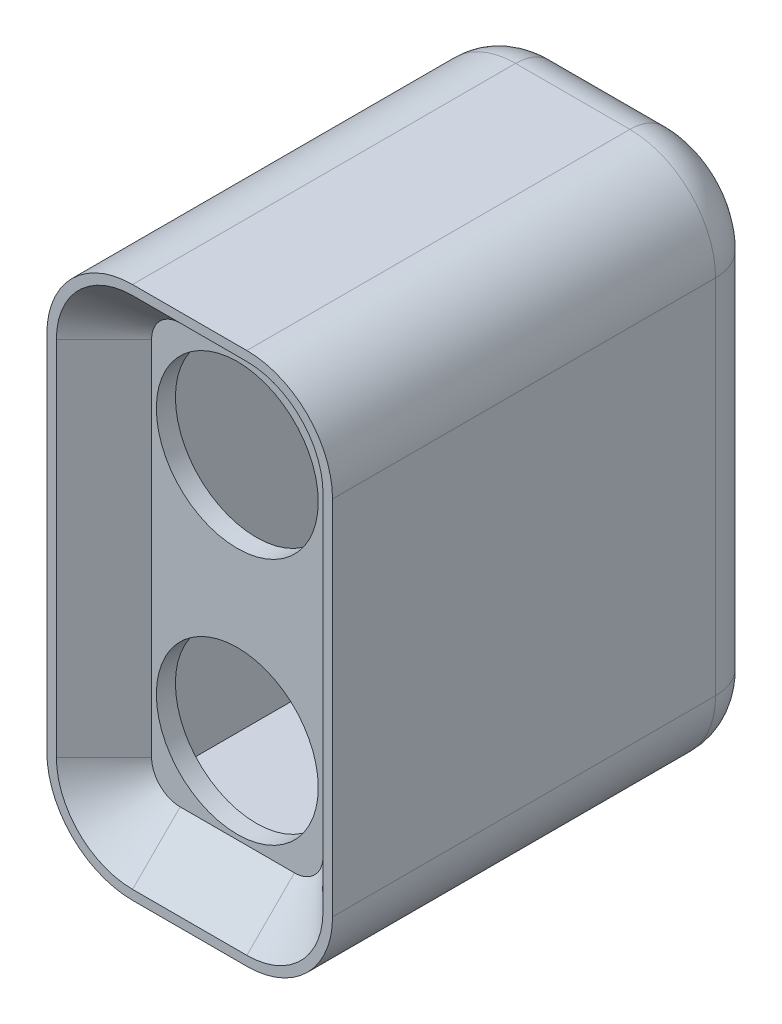
SolidWorks part; units mm, degrees
ref_plane "Front Plane" through (0, 0, 0) normal (0, 0, 1) x (1, 0, 0)
ref_plane "Top Plane" through (0, 0, 0) normal (0, 1, 0) x (1, 0, 0)
ref_plane "Right Plane" through (0, 0, 0) normal (1, 0, 0) x (0, 0, -1)
sketch "Sketch1" plane through (0, 0, 0) normal (0, 0, 1) x (1, 0, 0)
  line L0 (0, -14.84) -> (0, 41.16) construction
  line L1 (-15, -14.84) -> (15, -14.84)
  line L2 (-15, -14.84) -> (-15, 41.16)
  line L3 (-15, 41.16) -> (15, 41.16)
  line L4 (15, -14.84) -> (15, 41.16)
  line L5 (-15, 13.16) -> (15, 13.16) construction
  line L6 (15, 13.16) -> (0, 26.16) construction
  line L7 (15, 13.16) -> (0, 0.16) construction
  line L9 (-15, 3.7375) -> (-9, 3.7375) construction
  line L10 (9, -12.34) -> (-9, -12.34)
  line L11 (9, -12.34) -> (9, 38.66)
  line L12 (9, 38.66) -> (-9, 38.66)
  line L13 (-9, -12.34) -> (-9, 38.66)
  line L14 (9, -12.34) -> (-9, 38.66) construction
  line L15 (9, 38.66) -> (-9, -12.34) construction
  line L16 (3.386, -14.84) -> (3.386, -12.34) construction
  circle A0 centre (0, 0.16) radius 8.5
  circle A1 centre (0, 26.16) radius 8.5
  point P19 (0, 13.16)
  dimension "D1" = 17
  dimension "D4" = 43
  dimension "D2" = 9
  dimension "D3" = 26
  dimension "D6" = 2.5
  dimension "D7" = 4
  dimension "D8" = 0.5
extrude "Boss-Extrude1" add sketch "Sketch1" against normal blind 2 contours L13 L10 L11 L12 A1 A0 | L1 L4 L3 L2 L10 L13 L12 L11
sketch "Sketch2" plane through (0, 0, 0) normal (0, 0, 1) x (1, 0, 0)
  line L1 (-6.6343, -14.84) -> (-6.6343, -8.84) construction
  line L2 (9, -8.84) -> (-9, -8.84)
  line L3 (9, -8.84) -> (9, 35.16)
  line L4 (9, 35.16) -> (-9, 35.16)
  line L5 (-15, -14.84) -> (15, -14.84)
  line L6 (15, -14.84) -> (15, 41.16)
  line L7 (15, 41.16) -> (-15, 41.16)
  line L8 (-15, 41.16) -> (-15, -14.84)
  line L9 (-15, -14.84) -> (15, -14.84)
  line L10 (15, -14.84) -> (15, 41.16)
  line L11 (15, 41.16) -> (-15, 41.16)
  line L12 (-15, 41.16) -> (-15, -14.84)
  line L13 (-9, -8.84) -> (-9, 35.16)
  line L14 (9, -8.84) -> (-9, 35.16) construction
  line L15 (9, 35.16) -> (-9, -8.84) construction
  line L16 (-15, 3.0651) -> (-9, 3.0651) construction
  circle A0 centre (0, 0.16) radius 8.5 construction
  point P0 (0, 13.16)
  point P16 (0, 0)
  dimension "D3" = 0.5
  dimension "D1" = 0
extrude "Boss-Extrude2" add sketch "Sketch2" along normal blind 5
fillet "Fillet1" radius 9 4 edges at (15, 41.16, 1.5) (15, -14.84, 1.5) (-15, 41.16, 1.5) (-15, -14.84, 1.5)
sketch "Sketch3" plane through (0, 0, 5) normal (0, 0, 1) x (1, 0, 0)
  line L0 (-9, 35.16) -> (-9, -8.84) construction
  circle A1 centre (0, 0.16) radius 8.5 construction
  circle A3 centre (0, 0.16) radius 9
  dimension "D1" = 18
fillet "Fillet3" radius 3 4 edges at (9, 35.16, 2.5) (-9, 35.16, 2.5) (9, -8.84, 2.5) (-9, -8.84, 2.5)
chamfer "Chamfer3" distance 5 distance2 5 8 edges at (9, 13.16, 5) (8.1213, 34.2813, 5) (8.1213, -7.9613, 5) (-8.1213, 34.2813, 5) (-8.1213, -7.9613, 5) (-9, 13.16, 5) (0, 35.16, 5) (0, -8.84, 5)
sketch "Sketch4" plane through (0, 0, -2) normal (0, 0, -1) x (-1, 0, 0)
  line L0 (15, 13.16) -> (-19.2215, 13.16) construction
  line L1 (-10.25, 35.66) -> (10.25, 35.66) construction
  line L2 (-12.0414, 35.76) -> (10.35, 35.76)
  line L3 (-12.0414, 35.76) -> (-12.0414, -9.44)
  line L4 (6, 41.16) -> (-6, 41.16)
  line L5 (-15, 32.16) -> (-15, -5.84)
  line L6 (-6, -14.84) -> (6, -14.84)
  line L7 (15, -5.84) -> (15, 32.16)
  line L8 (6, 41.16) -> (-6, 41.16)
  line L9 (-15, 32.16) -> (-15, -5.84)
  line L10 (-6, -14.84) -> (6, -14.84)
  line L11 (15, -5.84) -> (15, 32.16)
  line L12 (-12.0414, -9.44) -> (10.35, -9.44)
  line L13 (10.35, 35.76) -> (10.35, -9.44)
  line L14 (-12.0414, 35.76) -> (10.35, -9.44) construction
  line L15 (-12.0414, -9.44) -> (10.35, 35.76) construction
  line L16 (10.25, 35.66) -> (10.25, -9.34) construction
  line L17 (-11.9414, 3.16) -> (-11.9414, 0.648) construction
  arc A4 (-6, 41.16) -> (-15, 32.16) centre (-6, 32.16) ccw
  arc A5 (-15, -5.84) -> (-6, -14.84) centre (-6, -5.84) ccw
  arc A6 (6, -14.84) -> (15, -5.84) centre (6, -5.84) ccw
  arc A7 (15, 32.16) -> (6, 41.16) centre (6, 32.16) ccw
  arc A8 (-6, 41.16) -> (-15, 32.16) centre (-6, 32.16) ccw
  arc A9 (-15, -5.84) -> (-6, -14.84) centre (-6, -5.84) ccw
  arc A10 (6, -14.84) -> (15, -5.84) centre (6, -5.84) ccw
  arc A11 (15, 32.16) -> (6, 41.16) centre (6, 32.16) ccw
  point P12 (-0.8457, 13.16)
  dimension "D2" = 0.1
  dimension "D3" = 0.1
  dimension "D4" = 0.1
  dimension "D1" = 0
extrude "Boss-Extrude3" add sketch "Sketch4" along normal up to surface (38.219 mm away)
sketch "Sketch5" plane through (0, 0, -40.219) normal (0, 0, -1) x (-1, 0, 0)
  line L0 (15, 13.16) -> (-22.3081, 13.16) construction
  line L1 (-9.44, 6.56) -> (5.75, 6.56) construction
  line L2 (5.85, 19.86) -> (-9.54, 19.86)
  line L3 (5.85, 19.86) -> (5.85, 6.46)
  line L4 (15, -5.84) -> (15, 32.16)
  line L5 (6, 41.16) -> (-6, 41.16)
  line L6 (-15, 32.16) -> (-15, -5.84)
  line L7 (-6, -14.84) -> (6, -14.84)
  line L8 (15, -5.84) -> (15, 32.16)
  line L9 (6, 41.16) -> (-6, 41.16)
  line L10 (-15, 32.16) -> (-15, -5.84)
  line L11 (-6, -14.84) -> (6, -14.84)
  line L12 (5.85, 6.46) -> (-9.54, 6.46)
  line L13 (-9.54, 19.86) -> (-9.54, 6.46)
  line L14 (5.85, 19.86) -> (-9.54, 6.46) construction
  line L15 (5.85, 6.46) -> (-9.54, 19.86) construction
  line L16 (5.75, 6.56) -> (5.75, 19.76) construction
  line L17 (-9.44, 6.56) -> (-9.44, 19.76) construction
  arc A4 (15, 32.16) -> (6, 41.16) centre (6, 32.16) ccw
  arc A5 (-6, 41.16) -> (-15, 32.16) centre (-6, 32.16) ccw
  arc A6 (-15, -5.84) -> (-6, -14.84) centre (-6, -5.84) ccw
  arc A7 (6, -14.84) -> (15, -5.84) centre (6, -5.84) ccw
  arc A8 (15, 32.16) -> (6, 41.16) centre (6, 32.16) ccw
  arc A9 (-6, 41.16) -> (-15, 32.16) centre (-6, 32.16) ccw
  arc A10 (-15, -5.84) -> (-6, -14.84) centre (-6, -5.84) ccw
  arc A11 (6, -14.84) -> (15, -5.84) centre (6, -5.84) ccw
  point P12 (-1.845, 13.16)
  line M13 (10.35, 35.76) -> (10.35, -9.44)
  line M14 (10.35, -9.44) -> (-12.0414, -9.44)
  line M15 (-12.0414, -9.44) -> (-12.0414, 35.76)
  line M16 (-12.0414, 35.76) -> (10.35, 35.76)
  line M17 (15, -5.84) -> (15, 32.16)
  arc M18 (15, 32.16) -> (6, 41.16) centre (6, 32.16) ccw
  line M19 (6, 41.16) -> (-6, 41.16)
  arc M20 (-6, 41.16) -> (-15, 32.16) centre (-6, 32.16) ccw
  line M21 (-15, 32.16) -> (-15, -5.84)
  arc M22 (-15, -5.84) -> (-6, -14.84) centre (-6, -5.84) ccw
  line M23 (-6, -14.84) -> (6, -14.84)
  arc M24 (6, -14.84) -> (15, -5.84) centre (6, -5.84) ccw
  dimension "D2" = 0.1
  dimension "D3" = 0.1
  dimension "D4" = 0.1
  dimension "D1" = 0
extrude "Boss-Extrude4" add sketch "Sketch5" against normal up to vertex (2.6 mm away) contours L13 L2 L3 L12 M13 M16 M15 M14 | M24 M17 M18 M19 M20 M21 M22 M23 M16 M13 M14 M15 | L8 A8 L9 A9 L10 A10 L11 A11
fillet "Fillet4" radius 5 8 edges at (-15, 13.16, -40.219) (-12.364, -12.204, -40.219) (0, -14.84, -40.219) (12.364, -12.204, -40.219) (15, 13.16, -40.219) (12.364, 38.524, -40.219) (0, 41.16, -40.219) (-12.364, 38.524, -40.219)
